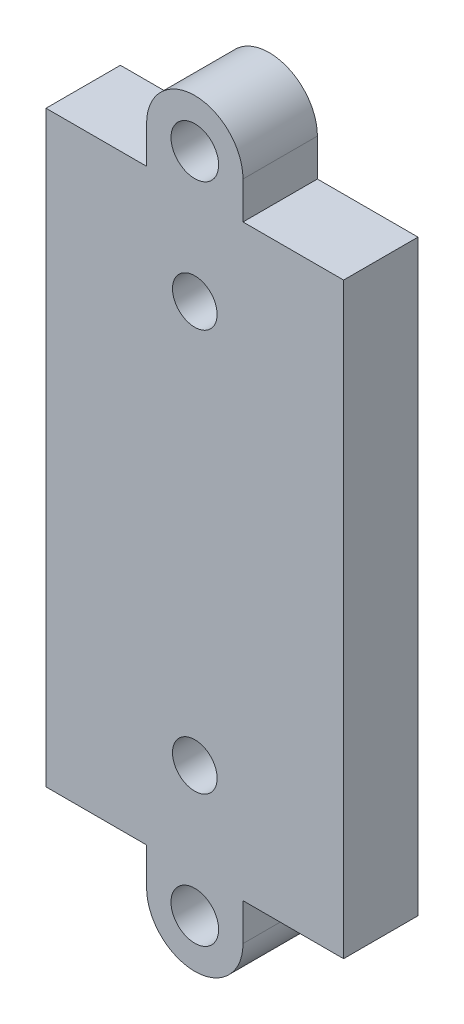
SolidWorks part; units mm, degrees
ref_plane "Plan de face" through (0, 0, 0) normal (0, 0, 1) x (1, 0, 0)
ref_plane "Plan de dessus" through (0, 0, 0) normal (0, 1, 0) x (1, 0, 0)
ref_plane "Plan de droite" through (0, 0, 0) normal (1, 0, 0) x (0, 0, -1)
sketch "Esquisse1" plane through (0, 0, 0) normal (0, 0, 1) x (1, 0, 0)
  line L0 (-13.5846, -30.0471) -> (-13.5846, -25.5471)
  line L1 (-13.8346, -25.2971) -> (-16.3346, -25.2971)
  line L2 (-16.5846, -25.0471) -> (-16.5846, 6.4529)
  line L3 (-16.3346, 6.7029) -> (-13.8346, 6.7029)
  line L4 (-13.5846, 6.9529) -> (-13.5846, 11.4529)
  line L5 (-13.3346, 11.7029) -> (-8.5846, 11.7029)
  line L6 (-8.5846, 11.7029) -> (-8.5846, 6.7029)
  line L7 (-8.5846, 6.7029) -> (-7.4918, 6.7029)
  line L8 (-7.4918, 6.7029) -> (-4.0345, 6.7029)
  line L9 (-4.0345, -25.2971) -> (-7.4918, -25.2971)
  line L10 (-7.4918, -25.2971) -> (-8.5846, -25.2971)
  line L11 (-8.5846, -25.2971) -> (-8.5846, -30.2971)
  line L12 (-8.5846, -30.2971) -> (-13.3346, -30.2971)
  line L13 (-13.3346, -30.2971) -> (-13.5846, -30.2971)
  line L14 (-13.5846, -30.2971) -> (-13.5846, -30.0471)
  line L15 (-13.5846, -25.5471) -> (-13.5846, -25.2971)
  line L16 (-13.5846, -25.2971) -> (-13.8346, -25.2971)
  line L17 (-16.3346, -25.2971) -> (-16.5846, -25.2971)
  line L18 (-16.5846, -25.2971) -> (-16.5846, -25.0471)
  line L19 (-16.3346, 6.7029) -> (-16.5846, 6.7029)
  line L20 (-16.5846, 6.7029) -> (-16.5846, 6.4529)
  line L21 (-13.5846, 6.9529) -> (-13.5846, 6.7029)
  line L22 (-13.5846, 6.7029) -> (-13.8346, 6.7029)
  line L23 (-13.5846, 11.4529) -> (-13.5846, 11.7029)
  line L24 (-13.5846, 11.7029) -> (-13.3346, 11.7029)
  arc A0 (3.4488, 4.7029) -> (-4.0345, 6.7029) centre (-4.0345, -8.2971) ccw
  arc A1 (3.4488, 4.7029) -> (18.4154, 0.7029) centre (18.4154, 30.7029) ccw
  arc A2 (18.4154, -19.2971) -> (18.4154, 0.7029) centre (18.4154, -9.2971) ccw
  arc A3 (18.4154, -19.2971) -> (3.4488, -23.2971) centre (18.4154, -49.2971) ccw
  arc A4 (-4.0345, -25.2971) -> (3.4488, -23.2971) centre (-4.0345, -10.2971) ccw
  circle A5 centre (18.4779, -2.2971) radius 1
  circle A6 centre (25.4154, -9.3596) radius 1
  circle A7 centre (18.4154, -9.2971) radius 1.5
  circle A8 centre (11.4154, -9.2347) radius 1
  circle A9 centre (18.3529, -16.2971) radius 1
extrude "Boss.-Extru.1" add sketch "Esquisse1" along normal blind 5
sketch "Esquisse2" plane through (0, 0, 0) normal (0, 0, -1) x (-1, 0, 0)
  line L0 (-18.4154, -9.2971) -> (7.3764, -9.2971) construction
  line L2 (1.5846, -19.2971) -> (1.5846, -26.2971) construction
  line L3 (4.0345, 6.7029) -> (8.5846, 6.7029) construction
  line L4 (1.5846, -19.2971) -> (1.5846, -25.2971)
  line L5 (-26.8332, -33.657) -> (-26.1987, -19.2971)
  line L6 (21.5846, -33.657) -> (-26.8332, -33.657)
  line L7 (21.5846, 7.7029) -> (1.5846, 7.7029)
  line L8 (21.5846, -26.2971) -> (21.5846, -33.657)
  line L9 (1.5846, 6.7029) -> (1.5846, 7.7029)
  line L10 (-26.1987, -19.2971) -> (1.5846, -19.2971)
  line L11 (1.5846, -25.2971) -> (1.5846, -26.2971)
  line L12 (-26.1987, 0.7029) -> (1.5846, 0.7029)
  line L13 (21.5846, -26.2971) -> (1.5846, -26.2971)
  line L15 (21.5846, 7.7029) -> (21.5846, 15.0627)
  line L16 (21.5846, 15.0627) -> (-26.8332, 15.0627)
  line L17 (-26.8332, 15.0627) -> (-26.1987, 0.7029)
  line L18 (1.5846, 0.7029) -> (1.5846, 7.7029) construction
  line L19 (1.5846, 0.7029) -> (1.5846, 6.7029)
  arc A1 (-18.4154, 0.7029) -> (-18.4154, -19.2971) centre (-18.4154, -9.2971) ccw construction
extrude "Enlèv. mat.-Extru.1" cut sketch "Esquisse2" against normal blind 5
sketch "Esquisse3" plane through (0, 0, 0) normal (0, 0, -1) x (-1, 0, 0)
  line L0 (8.5846, 7.7029) -> (13.5846, 7.7029) construction
  line L1 (21.5846, -26.2971) -> (1.5846, -26.2971)
  line L2 (21.5846, -26.2971) -> (21.5846, 7.7029)
  line L3 (21.5846, 7.7029) -> (1.5846, 7.7029)
  line L4 (1.5846, -26.2971) -> (1.5846, 7.7029)
  line L5 (13.5846, -26.2971) -> (8.5846, -26.2971) construction
  dimension "D1" = 0
  dimension "D2" = 20
  dimension "D3" = 0
extrude "Boss.-Extru.2" add sketch "Esquisse3" against normal blind 5
sketch "Esquisse4" plane through (0, 0, 0) normal (0, 0, -1) x (-1, 0, 0)
  line L1 (21.5846, -26.2971) -> (1.5846, -26.2971) construction
  line L2 (1.5846, -26.2971) -> (1.5846, -19.2971) construction
  line L4 (28.8831, -28.9494) -> (19.0846, -28.9494)
  line L5 (28.8831, -28.9494) -> (28.8831, 10.9087)
  line L6 (28.8831, 10.9087) -> (19.0846, 10.9087)
  line L7 (19.0846, -28.9494) -> (19.0846, 10.9087)
  circle A0 centre (9.0846, -22.7971) radius 1.5
  circle A1 centre (9.0846, 4.2029) radius 1.5
  dimension "D1" = 7.5
  dimension "D4" = 3
  dimension "D5" = 3
  dimension "D6" = 10
  dimension "D2" = 27
  dimension "D3" = 3.5
extrude "Enlèv. mat.-Extru.2" cut sketch "Esquisse4" against normal blind 5
sketch "Esquisse5" plane through (0, 0, 0) normal (0, 0, -1) x (-1, 0, 0)
  line L1 (1.5846, -26.2971) -> (-0.9154, -26.2971)
  line L2 (1.5846, -26.2971) -> (1.5846, 7.7029)
  line L3 (1.5846, 7.7029) -> (-0.9154, 7.7029)
  line L4 (-0.9154, -26.2971) -> (-0.9154, 7.7029)
  circle A0 centre (9.0846, -22.7971) radius 1.5 construction
  dimension "D1" = 10
extrude "Boss.-Extru.3" add sketch "Esquisse5" against normal up to vertex (5 mm away) up to point (-1.5846, -26.2971, 5)
sketch "Esquisse6" plane through (0, 0, 0) normal (0, 0, -1) x (-1, 0, 0)
  line L0 (19.0846, -26.2971) -> (-0.9154, -26.2971) construction
  line L1 (-0.9154, 7.7029) -> (19.0846, 7.7029) construction
  line L2 (12.3246, -25.1248) -> (5.8446, -25.1248)
  line L4 (12.3246, -28.7971) -> (12.3246, -25.1248)
  line L6 (5.8446, -28.7971) -> (5.8446, -25.1248)
  line L7 (12.3246, 6.7577) -> (5.8446, 6.7577)
  line L8 (5.8446, 6.7577) -> (5.8446, 10.2029)
  line L9 (12.3246, 6.7577) -> (12.3246, 10.2029)
  circle A0 centre (9.0846, -28.7971) radius 1.6
  circle A1 centre (9.0846, 10.2029) radius 1.6
  arc A2 (5.8446, -28.7971) -> (12.3246, -28.7971) centre (9.0846, -28.7971) ccw
  arc A3 (12.3246, 10.2029) -> (5.8446, 10.2029) centre (9.0846, 10.2029) ccw
  circle A5 centre (9.0846, -22.7971) radius 1.5 construction
  dimension "D1" = 3.2
  dimension "D2" = 3.2
  dimension "D3" = 2.5
  dimension "D4" = 2.5
  dimension "D5" = 0
  dimension "D6" = 6.48
  dimension "D7" = 6.48
extrude "Boss.-Extru.4" add sketch "Esquisse6" against normal up to vertex (5 mm away) up to point (-19.0846, 7.7029, 5)
fillet "Congé1" radius 10 2 edges at (0.9154, 0.7029, 2.5) (0.9154, -19.2971, 2.5)
sketch "Esquisse7" plane through (0, 0, 0) normal (0, 0, -1) x (-1, 0, 0)
  line L0 (19.0846, 7.7029) -> (19.0846, -26.2971) construction
  line L1 (-0.9154, -33.6307) -> (-41.1669, -33.6307)
  line L2 (-0.9154, -33.6307) -> (-0.9154, 11.4484)
  line L3 (-0.9154, 11.4484) -> (-41.1669, 11.4484)
  line L4 (-41.1669, -33.6307) -> (-41.1669, 11.4484)
  dimension "D1" = 20
extrude "Enlèv. mat.-Extru.3" cut sketch "Esquisse7" against normal blind 10
sketch "Esquisse8" plane through (0, 0, 0) normal (0, 0, -1) x (-1, 0, 0)
  line L0 (-0.9154, -26.2971) -> (-0.9154, 7.7029) construction
  line L1 (19.0846, -26.2971) -> (-0.9154, -26.2971)
  line L2 (19.0846, -26.2971) -> (19.0846, 13.2029)
  line L3 (19.0846, 13.2029) -> (-0.9154, 13.2029)
  line L4 (-0.9154, -26.2971) -> (-0.9154, 13.2029)
  line L5 (19.0846, -6.5471) -> (-0.9154, -6.5471) construction
  circle A0 centre (9.0846, -22.7971) radius 1.5 construction
  circle A1 centre (9.0846, -22.7971) radius 1.5
  dimension "D1" = 39.5
extrude "Boss.-Extru.5" add sketch "Esquisse8" against normal up to vertex (5 mm away) up to point (-19.0846, 7.7029, 5)
sketch "Esquisse9" plane through (0, 0, 0) normal (0, 0, -1) x (-1, 0, 0)
  line L0 (19.0846, -6.5471) -> (-0.9154, -6.5471) construction
  line L1 (19.0846, 13.2029) -> (19.0846, -26.2971) construction
  line L2 (-0.9154, -26.2971) -> (-0.9154, 13.2029) construction
  line L3 (5.8446, -26.2971) -> (5.8446, -28.7971) construction
  line L4 (12.3246, -28.7971) -> (12.3246, -26.2971) construction
  line L5 (19.0846, 13.2029) -> (10.3084, 13.2029) construction
  line L6 (7.8608, 13.2029) -> (-0.9154, 13.2029) construction
  line L7 (12.3246, 15.7029) -> (12.3246, 13.2029)
  line L8 (5.8446, 13.2029) -> (5.8446, 15.7029)
  line L9 (12.3246, 13.2029) -> (10.3084, 13.2029)
  line L10 (7.8608, 13.2029) -> (5.8446, 13.2029)
  circle A1 centre (9.0846, -28.7971) radius 1.6 construction
  arc A2 (5.8446, -28.7971) -> (12.3246, -28.7971) centre (9.0846, -28.7971) ccw construction
  arc A5 (10.3084, 13.2029) -> (7.8608, 13.2029) centre (9.0846, 10.2029) ccw construction
  arc A6 (5.8446, 15.7029) -> (12.3246, 15.7029) centre (9.0846, 15.7029) cw
  circle A7 centre (9.0846, 15.7029) radius 1.6
  arc A9 (10.3084, 13.2029) -> (7.8608, 13.2029) centre (9.0846, 10.2029) ccw
extrude "Boss.-Extru.6" add sketch "Esquisse9" against normal up to vertex (5 mm away) up to point (-19.0846, 13.2029, 5)
sketch "Esquisse10" plane through (0, 0, 0) normal (0, 0, -1) x (-1, 0, 0)
  line L0 (19.0846, -6.5471) -> (-0.9154, -6.5471) construction
  line L1 (19.0846, 13.2029) -> (19.0846, -26.2971) construction
  line L2 (-0.9154, -26.2971) -> (-0.9154, 13.2029) construction
  circle A0 centre (9.0846, -22.7971) radius 1.5 construction
  circle A2 centre (9.0846, 9.7029) radius 1.5
extrude "Enlèv. mat.-Extru.4" cut sketch "Esquisse10" against normal blind 10
sketch "Esquisse11" plane through (0, 0, 0) normal (0, 0, -1) x (-1, 0, 0)
  line L0 (-0.9154, -26.2971) -> (-0.9154, 13.2029) construction
  line L1 (5.8446, -26.2971) -> (-0.9154, -26.2971) construction
  line L2 (19.0846, -6.5471) -> (-0.9154, -6.5471) construction
  line L3 (19.0846, 13.2029) -> (19.0846, -26.2971) construction
  circle A0 centre (9.0846, -20.0471) radius 1.5
  circle A1 centre (9.0846, 6.9529) radius 1.5
  dimension "D1" = 3
  dimension "D2" = 10
  dimension "D3" = 6.25
extrude "Enlèv. mat.-Extru.5" cut sketch "Esquisse11" against normal blind 10
sketch "Esquisse12" plane through (0, 0, 0) normal (0, 0, -1) x (-1, 0, 0)
  arc A1 (9.6841, 8.3279) -> (8.4851, 8.3279) centre (9.0846, 9.7029) ccw construction
  arc A3 (8.4851, -21.4221) -> (9.6841, -21.4221) centre (9.0846, -22.7971) ccw construction
  arc A5 (9.6841, 8.3279) -> (8.4851, 8.3279) centre (9.0846, 9.7029) ccw
  arc A7 (8.4851, -21.4221) -> (9.6841, -21.4221) centre (9.0846, -22.7971) ccw
  arc A8 (8.4851, -21.4221) -> (9.6841, -21.4221) centre (9.0846, -20.0471) ccw
  arc A9 (9.6841, 8.3279) -> (8.4851, 8.3279) centre (9.0846, 6.9529) ccw
extrude "Boss.-Extru.7" add sketch "Esquisse12" against normal up to vertex (5 mm away) up to point (-19.0846, -26.2971, 5)
